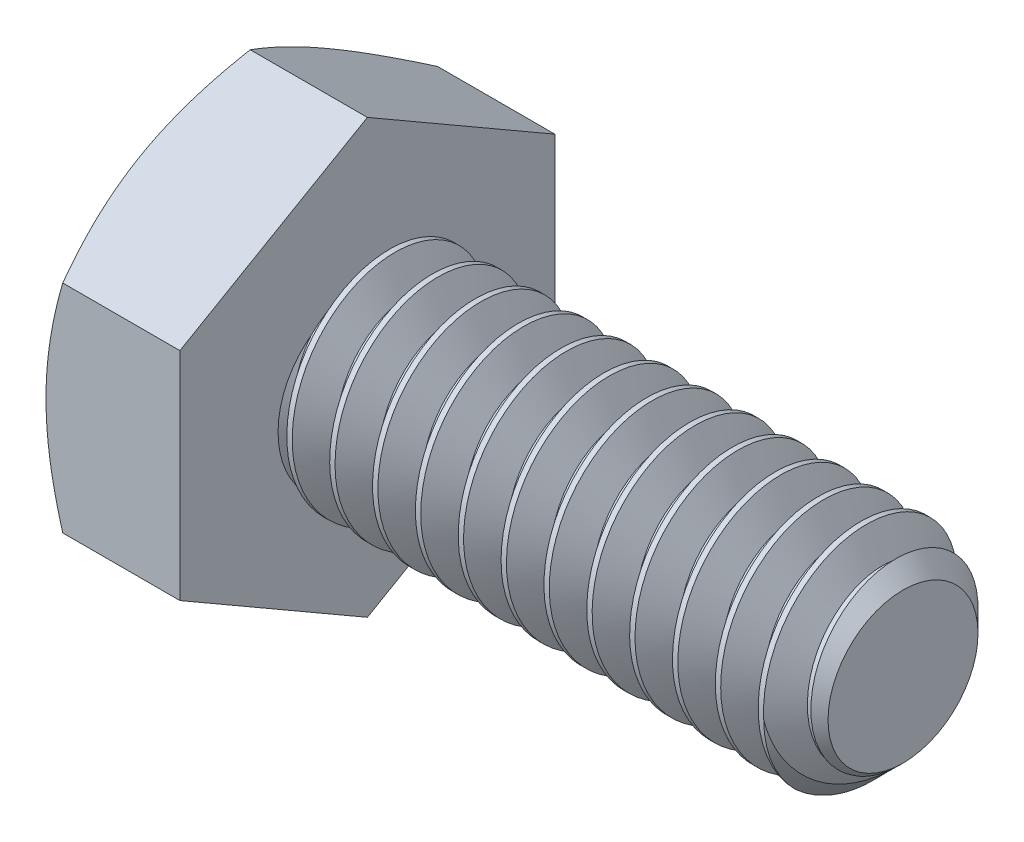
SolidWorks part; units mm, degrees
note: '?' marks a value the reader was unsure of.
ref_plane "Front Plane" through (0, 0, 0) normal (0, 0, 1) x (1, 0, 0)
ref_plane "Top Plane" through (0, 0, 0) normal (0, 1, 0) x (1, 0, 0)
ref_plane "Right Plane" through (0, 0, 0) normal (1, 0, 0) x (0, 0, -1)
sketch "Sketch1" plane through (0, 0, 0) normal (0, 0, 1) x (1, 0, 0)
  line L0 (-9.9219, 0) -> (9.9219, 0) construction
  line L1 (9.9219, 3.175) -> (9.9219, -3.175) construction
  line L2 (-5.9531, 5.5562) -> (-5.9531, -5.5562) construction
  line L3 (-9.9219, 5.5562) -> (-9.9219, -5.5562) construction
  point P9 (-5.9531, 0)
  point P10 (5.4769, -3.175)
  point P12 (-9.9219, 5.5562)
  point P13 (-5.9531, 5.5562)
  point P14 (9.9219, 3.175)
  dimension "Screw Dia" = 6.35
  dimension "Hex" = 11.1125
  dimension "Head Ht" = 3.9688
  dimension "Screw Lenght" = 15.875
  dimension "D1" = 4.445
ref_plane "Plane2" through (9.9219, 0, 0) normal (1, 0, 0) x (0, 0, -1)
sketch "Sketch5" plane through (9.9219, 0, 0) normal (1, 0, 0) x (0, 0, -1)
  circle A0 centre (0, 0) radius 3.175
extrude "Boss-Extrude3" add sketch "Sketch5" against normal up to vertex (15.875 mm away) up to point (-5.9531, 0, 0)
sketch "Sketch9" plane through (9.9219, 0, 0) normal (1, 0, 0) x (0, 0, -1)
  circle A1 centre (0, 0) radius 3.175
  circle A2 centre (0, 0) radius 3.175
  dimension "D1" = 0
curve "Helix/Spiral1" pitch 1.27 height 17.145 turns 13.5 parameters "Pitch"=1.27
chamfer "Chamfer1" distance 0.9525 angle 45 1 edges at (9.9219, 0, -3.175)
sketch "Sketch11" plane through (-5.9531, 0, 0) normal (-1, 0, 0) x (0, 0, 1)
  line L1 (0, 6.4158) -> (-5.5562, 3.2079)
  line L2 (-5.5562, 3.2079) -> (-5.5563, -3.2079)
  line L3 (-5.5563, -3.2079) -> (0, -6.4158)
  line L4 (0, -6.4158) -> (5.5562, -3.2079)
  line L5 (5.5562, -3.2079) -> (5.5563, 3.2079)
  line L6 (5.5563, 3.2079) -> (0, 6.4158)
  circle A0 centre (0, 0) radius 5.5562 construction
extrude "Boss-Extrude4" add sketch "Sketch11" along normal up to vertex (3.9688 mm away) up to point (-9.9219, -5.5562, 0)
sketch "Sketch12" plane through (-9.9219, 0, 0) normal (-1, 0, 0) x (0, 0, 1)
  circle A0 centre (0, 0) radius 5.5562 construction
  circle A1 centre (0, 0) radius 5.5562
extrude "Cut-Extrude1" cut sketch "Sketch12" against normal through all draft 60 flip side to cut
sketch "Sketch14" plane through (-9.9219, 0, 0) normal (-1, 0, 0) x (0, 0, 1)
  line L0 (-5.5562, 3.2079) -> (5.5563, 3.2079) construction
  point P5 (-5.5562, 3.2079)
  point P6 (5.5563, 3.2079)
sketch "Sketch15" plane through (0, 0, 0) normal (0, 0, 1) x (1, 0, 0)
  point P0 (-5.9531, 6.4158)
  point P1 (-9.9219, 5.5562)
  point P3 (9.9219, 2.2225)
ref_axis "Center Axis" through (-20.108, 0, 0) along (1, 0, 0)?
sketch "Sketch10" plane through (0, 0, 0) normal (0, 0, 1) x (1, 0, 0)
  line L0 (9.9219, 3.175) -> (10.3981, 2.3501)
  line L1 (10.3981, 2.3501) -> (10.5569, 2.3501)
  line L2 (10.5569, 2.3501) -> (11.0331, 3.175)
  line L3 (9.9219, 3.175) -> (11.0331, 3.175)
  line L4 (10.4775, 3.175) -> (10.4775, 2.3501) construction
  line L5 (10.16, 2.7626) -> (10.795, 2.7626) construction
  dimension "D1" = 60
  dimension "D2" = 0.1588
  dimension "D3" = 0.635
sweep "Cut-Sweep1" cut profiles "Sketch10" path "Helix/Spiral1" align with end faces yes
sketch "Sketch13" plane through (-5.9531, 0, 0) normal (1, 0, 0) x (0, 0, -1)
  line L6 (0, 6.4158) -> (-5.5563, 3.2079)
  line L7 (-5.5563, 3.2079) -> (-5.5562, -3.2079)
  line L8 (-5.5562, -3.2079) -> (0, -6.4158)
  line L9 (0, -6.4158) -> (5.5563, -3.2079)
  line L10 (5.5563, -3.2079) -> (5.5562, 3.2079)
  line L11 (5.5562, 3.2079) -> (0, 6.4158)
  line L12 (0, 6.4158) -> (-5.5563, 3.2079)
  line L13 (-5.5563, 3.2079) -> (-5.5562, -3.2079)
  line L14 (-5.5562, -3.2079) -> (0, -6.4158)
  line L15 (0, -6.4158) -> (5.5563, -3.2079)
  line L16 (5.5563, -3.2079) -> (5.5562, 3.2079)
  line L17 (5.5562, 3.2079) -> (0, 6.4158)
  dimension "D1" = 0
extrude "Boss-Extrude5" add sketch "Sketch13" against normal up to vertex (3.4725 mm away) up to point (-9.4256, 3.2079, 5.5563)
equation "\"D2@Sketch10\" = \"Pitch@Helix/Spiral1\"*.125"
equation "\"D3@Sketch10\" = \"Pitch@Helix/Spiral1\"*.5"
equation "\"D3@Helix/Spiral1\" = \"Screw Lenght@Sketch1\"+\"Pitch@Helix/Spiral1\""
equation "\"D1@Chamfer1\" = \"Pitch@Helix/Spiral1\"*.75"
equation "\"D1@Sketch1\" = \"Pitch@Helix/Spiral1\"*3.5"
